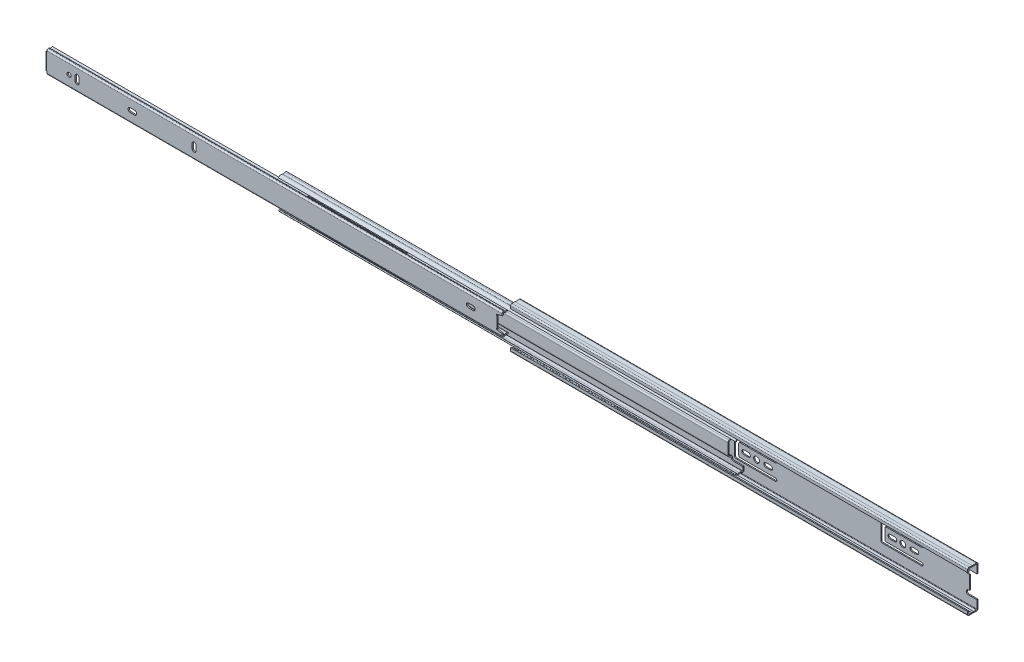
SolidWorks part; units mm, degrees
ref_plane "Front" through (0, 0, 0) normal (0, 0, 1) x (1, 0, 0)
ref_plane "Top" through (0, 0, 0) normal (0, 1, 0) x (1, 0, 0)
ref_plane "Right" through (0, 0, 0) normal (1, 0, 0) x (0, 0, -1)
sketch "Sketch1" plane through (0, 0, 0) normal (1, 0, 0) x (0, 0, -1)
  line L1 (5.6388, 0) -> (-5.6388, 0) construction
  line L4 (-4.1393, 22.8203) -> (-0.7433, 22.6989)
  line L5 (-1.1312, 21.5182) -> (-4.1819, 21.6273)
  line L6 (-4.445, 18.415) -> (-5.6388, 18.415)
  line L7 (-4.445, 21.3734) -> (-4.445, 18.415)
  line L8 (-5.6388, 18.415) -> (-5.6388, 21.3734)
  line L9 (3.9237, 21.6269) -> (0.7619, 21.5441)
  line L10 (5.6388, 0) -> (5.6388, 21.1191)
  line L11 (4.445, 21.1191) -> (4.445, 0)
  line L12 (5.6388, 0) -> (4.445, 0)
  line L13 (-0.7433, 22.6989) -> (3.8925, 22.8203)
  arc A0 (-4.445, 21.3734) -> (-4.1819, 21.6273) centre (-4.191, 21.3734) cw
  arc A1 (-5.6388, 21.3734) -> (-4.1393, 22.8203) centre (-4.191, 21.3734) cw
  arc A3 (3.9237, 21.6269) -> (4.445, 21.1191) centre (3.937, 21.1191) cw
  arc A4 (3.8925, 22.8203) -> (5.6388, 21.1191) centre (3.937, 21.1191) cw
  arc A5 (-1.1312, 21.5182) -> (0.7619, 21.5441) centre (-0.1524, 19.1744) cw
  dimension "D2" = 19.1744
  dimension "D7" = 0.254
  dimension "D8" = 0.508
  dimension "D6" = 2.54
  dimension "D9" = 1.1938
  dimension "D10" = 88.5
  dimension "D1" = 11.2776
  dimension "D3" = 5.7912
  dimension "D4" = 36.83
  dimension "D5" = 1.1938
  dimension "D11" = 87.953
  dimension "D12" = 45.6406
extrude "Extrude1" add sketch "Sketch1" along normal mid plane 500.126
ref_plane "Travel / 2" through (-504.063, 0, 0) normal (-1, 0, 0) x (0, 0, 1)
sketch "Sketch2" plane through (-504.063, 0, 0) normal (-1, 0, 0) x (0, 0, 1)
  line L0 (0.0254, 6.1159) -> (0.0254, 0)
  line L2 (-5.6388, 0) -> (5.6388, 0) construction
  line L3 (5.6388, 21.3734) -> (5.6388, 18.415) construction
  line L7 (-4.445, 21.1191) -> (-4.445, 0) construction
  line L8 (-5.6388, 0) -> (-5.6388, 21.1191) construction
  line L13 (-3.5306, 16.3766) -> (-3.5306, 9.5217)
  line L46 (-2.3867, 7.7262) -> (-0.4146, 6.8065)
  arc A0 (0.0254, 6.1159) -> (-0.4146, 6.8065) centre (-0.7366, 6.1159) ccw
  arc A1 (-1.5056, 17.2916) -> (1.2415, 16.9143) centre (0.1524, 19.1744) ccw
  arc A4 (1.1312, 21.5182) -> (-0.7619, 21.5441) centre (0.1524, 19.1744) ccw construction
  arc A19 (-3.5306, 9.5217) -> (-2.3867, 7.7262) centre (-1.5494, 9.5217) ccw
  arc A25 (-1.5056, 17.2916) -> (-3.5306, 16.3766) centre (-2.3114, 16.3766) ccw
  arc A51 (5.7404, 15.6277) -> (1.2415, 16.9143) centre (2.7686, 13.7451) ccw
  dimension "D2" = 8.4074
  dimension "D3" = 27.4903
  dimension "D6" = 1.9812
  dimension "D8" = 12.2319
  dimension "D10" = 2.5088
  dimension "D11" = 1.2192
  dimension "D4" = 0.762
  dimension "D5" = 4.4704
  dimension "D7" = 115
  dimension "D9" = 19.0435
  dimension "D13" = 11.3792
extrude "Middle Member" add sketch "Sketch2" against normal blind 500.126 separate body thin thin type one direction reverse wall 1.2192
ref_plane "Travel" through (-758.063, 0, 0) normal (-1, 0, 0) x (0, 0, 1)
sketch "Sketch3" plane through (-758.063, 0, 0) normal (-1, 0, 0) x (0, 0, 1)
  line L0 (1.2446, 0) -> (0.0254, 0) construction
  line L1 (-5.6388, 0) -> (-5.6388, 21.1191) construction
  line L56 (7.0612, 0) -> (7.0612, 10.6235)
  line L93 (5.5372, 12.1475) -> (5.1643, 12.1475)
  arc A0 (1.2082, 11.9072) -> (4.2365, 11.8325) centre (2.7686, 13.7451) ccw
  arc A29 (7.0612, 10.6235) -> (5.5372, 12.1475) centre (5.5372, 10.6235) ccw
  arc A53 (5.1643, 12.1475) -> (4.2365, 11.8325) centre (5.1643, 10.6235) ccw
  dimension "D1" = 1.524
  dimension "D4" = 1.524
  dimension "D5" = 2.411
  dimension "D2" = 12.7
  dimension "D3" = 12.1475
  dimension "D6" = 5.853
extrude "Drawer Member" add sketch "Sketch3" against normal blind 500.126 thin thin type one direction wall 1.397
sketch "Sketch6" plane through (0, 0, 7.0612) normal (0, 0, 1) x (1, 0, 0)
  line L1 (-758.063, 0) -> (-756.158, 0)
  line L2 (-758.063, 0) -> (-758.063, 12.1475)
  line L3 (-758.063, 12.1475) -> (-756.158, 12.1475)
  line L4 (-756.158, 0) -> (-756.158, 12.1475)
  line L5 (-257.937, 12.1475) -> (-758.063, 12.1475) construction
  line L7 (-758.063, 10.6235) -> (-758.063, 0) construction
  line L8 (-257.937, 0) -> (-758.063, 0) construction
  dimension "D1" = 1.905
extrude "Cut-Extrude1" cut sketch "Sketch6" against normal through all
sketch "Sketch7" plane through (0, 0, 0) normal (0, -1, 0) x (1, 0, 0)
  line L0 (-756.158, 7.0612) -> (-756.412, 7.0612)
  line L1 (-758.063, 5.4102) -> (-758.063, 0.3041)
  line L2 (-758.063, 0.3041) -> (-756.666, 0.3041)
  line L3 (-756.666, 0.3041) -> (-756.666, 5.4102)
  line L4 (-756.412, 5.6642) -> (-756.158, 5.6642)
  line L5 (-257.937, 5.6642) -> (-756.158, 5.6642) construction
  line L6 (-756.158, 7.0612) -> (-756.158, 5.6642)
  line L7 (-257.937, 0.3041) -> (-756.158, 0.3041) construction
  line L9 (-756.158, 5.087) -> (-756.158, 0.3041) construction
  arc A0 (-756.412, 5.6642) -> (-756.666, 5.4102) centre (-756.412, 5.4102) ccw
  arc A1 (-756.412, 7.0612) -> (-758.063, 5.4102) centre (-756.412, 5.4102) ccw
  dimension "D1" = 0.254
  dimension "D2" = 1.905
extrude "Extrude4" add sketch "Sketch7" against normal blind 8.89
sketch "Sketch8" plane through (0, 0, -4.445) normal (0, 0, 1) x (1, 0, 0)
  line L0 (240.4245, 7.6456) -> (241.8588, 7.493)
  line L1 (250.063, 12.2048) -> (240.6664, 12.2048)
  line L2 (241.8588, 7.493) -> (241.8588, 0)
  line L3 (250.063, 0) -> (-250.063, 0) construction
  line L4 (250.063, 21.1191) -> (250.063, 0) construction
  line L5 (250.063, 12.2048) -> (250.063, 0)
  line L6 (250.063, 0) -> (241.8588, 0)
  arc A0 (240.6664, 12.2048) -> (240.4245, 7.6456) centre (240.6664, 9.9188) ccw
  dimension "D3" = 9.9188
  dimension "D1" = 12.2048
  dimension "D2" = 8.2042
  dimension "D4" = 9.3966
  dimension "D5" = 7.493
extrude "Cut-Extrude2" cut sketch "Sketch8" against normal up to next (1.1938 mm away)
sketch "Sketch11" plane through (0, 0, 7.0612) normal (0, 0, 1) x (1, 0, 0)
  line L0 (-263.652, 5.9678) -> (-263.652, 0)
  line L8 (-257.937, 8.5893) -> (-263.7963, 7.2212)
  line L11 (-263.652, 0) -> (-257.937, 0)
  line L12 (-257.937, 0) -> (-257.937, 8.5893)
  arc A1 (-263.7963, 7.2212) -> (-263.652, 5.9678) centre (-263.6519, 6.6028) ccw
  dimension "D3" = 0.635
  dimension "D1" = 5.715
  dimension "D2" = 8.5893
  dimension "D4" = 5.9678
  dimension "D5" = 103.143
extrude "Cut-Extrude3" cut sketch "Sketch11" against normal up to next (1.397 mm away)
sketch "Sketch12" plane through (0, 0, 1.2446) normal (0, 0, 1) x (1, 0, 0)
  line L0 (-3.937, 12.065) -> (-14.097, 12.065)
  line L1 (-3.937, 16.3766) -> (-3.937, 9.5217) construction
  line L2 (-16.637, 9.525) -> (-16.637, 0)
  line L3 (-3.937, 0) -> (-504.063, 0) construction
  line L4 (-16.637, 0) -> (-3.937, 0)
  line L5 (-3.937, 0) -> (-3.937, 12.065)
  arc A0 (-14.097, 12.065) -> (-16.637, 9.525) centre (-14.097, 9.525) ccw
  point P11 (-16.637, 12.065)
  dimension "D3" = 2.54
  dimension "D1" = 12.7
  dimension "D2" = 12.065
extrude "Cut-Extrude4" cut sketch "Sketch12" against normal through all
sketch "Sketch13" plane through (0, 0, -4.445) normal (0, 0, 1) x (1, 0, 0)
  line L0 (-181.6747, 7.112) -> (-206.5032, 7.112)
  line L1 (241.8588, 0) -> (-250.063, 0) construction
  line L2 (-189.7646, 0) -> (-189.7646, 4.2392) construction
  line L3 (-232.6017, 10.287) -> (-181.6747, 10.287)
  line L4 (-250.063, 21.1191) -> (-250.063, 0) construction
  line L5 (-210.3132, 7.112) -> (-232.6017, 7.112)
  line L6 (-209.5512, 0) -> (-209.5512, 6.35)
  line L7 (-207.2652, 6.35) -> (-207.2652, 0)
  line L8 (-187.2881, 2.286) -> (-192.2411, 2.286)
  line L13 (-226.3406, 0) -> (-221.7686, 0)
  line L14 (-218.238, 0) -> (-211.888, 0)
  line L15 (-209.5512, 0) -> (-207.2652, 0)
  line L16 (-204.7506, 0) -> (-200.1786, 0)
  line L17 (-194.5271, 0) -> (-185.0021, 0)
  arc A1 (-232.6017, 10.287) -> (-232.6017, 7.112) centre (-232.6017, 8.6995) ccw
  arc A2 (-209.5512, 6.35) -> (-210.3132, 7.112) centre (-210.3132, 6.35) ccw
  arc A4 (-206.5032, 7.112) -> (-207.2652, 6.35) centre (-206.5032, 6.35) ccw
  arc A7 (-181.6747, 7.112) -> (-181.6747, 10.287) centre (-181.6747, 8.6995) ccw
  arc A8 (-211.888, 0) -> (-218.238, 0) centre (-215.063, 0) ccw
  arc A9 (-221.7686, 0) -> (-226.3406, 0) centre (-224.0546, 0) ccw
  arc A10 (-200.1786, 0) -> (-204.7506, 0) centre (-202.4646, 0) ccw
  arc A11 (-185.0021, 0) -> (-187.2881, 2.286) centre (-187.2881, 0) ccw
  arc A12 (-192.2411, 2.286) -> (-194.5271, 0) centre (-192.2411, 0) ccw
  dimension "D3" = 2.286
  dimension "D4" = 3.175
  dimension "D7" = 8.9916
  dimension "D8" = 21.59
  dimension "D9" = 34.29
  dimension "D10" = 0.762
  dimension "D11" = 17.5387
  dimension "D12" = 9.525
  dimension "D13" = 5.5118
  dimension "D14" = 35
  dimension "D1" = 3.175
  dimension "D2" = 50.927
  dimension "D5" = 2.286
  dimension "D6" = 10.287
extrude "Cut-Extrude5" cut sketch "Sketch13" against normal up to next (1.1938 mm away)
sketch "Sketch32" plane through (0, 0, -5.6388) normal (0, 0, -1) x (-1, 0, 0)
  line L0 (69.6005, 0) -> (79.1255, 0)
  line L1 (83.888, 0) -> (90.238, 0)
  line L2 (93.7305, 0) -> (103.2555, 0)
  line L3 (106.621, 0) -> (111.193, 0)
  line L4 (-241.8588, 0) -> (185.0021, 0) construction
  line L5 (232.6017, 10.287) -> (181.6747, 10.287) construction
  line L6 (181.6747, 7.112) -> (206.5032, 7.112) construction
  line L7 (98.493, 2.286) -> (98.493, -3.4269) construction
  line L8 (74.363, 2.286) -> (74.363, -3.4269) construction
  line L14 (66.4255, 10.287) -> (109.669, 10.287)
  line L15 (105.097, 7.112) -> (66.4255, 7.112)
  line L17 (111.193, 8.763) -> (111.193, 0)
  line L18 (106.621, 0) -> (106.621, 5.588)
  line L23 (71.8865, 2.286) -> (76.8395, 2.286)
  line L25 (96.0165, 2.286) -> (100.9695, 2.286)
  arc A0 (218.238, 0) -> (211.888, 0) centre (215.063, 0) ccw construction
  arc A13 (111.193, 8.763) -> (109.669, 10.287) centre (109.669, 8.763) ccw
  arc A14 (106.621, 5.588) -> (105.097, 7.112) centre (105.097, 5.588) ccw
  arc A17 (66.4255, 10.287) -> (66.4255, 7.112) centre (66.4255, 8.6995) ccw
  arc A20 (79.1255, 0) -> (76.8395, 2.286) centre (76.8395, 0) ccw
  arc A21 (71.8865, 2.286) -> (69.6005, 0) centre (71.8865, 0) ccw
  arc A22 (90.238, 0) -> (83.888, 0) centre (87.063, 0) ccw
  arc A24 (103.2555, 0) -> (100.9695, 2.286) centre (100.9695, 0) ccw
  arc A25 (96.0165, 2.286) -> (93.7305, 0) centre (96.0165, 0) ccw
  dimension "D2" = 1.524
  dimension "D3" = 3.175
  dimension "D4" = 9.525
  dimension "D5" = 2.286
  dimension "D6" = 11.43
  dimension "D7" = 12.7
  dimension "D8" = 24.13
  dimension "D9" = 20.6375
  dimension "D10" = 128
  dimension "D1" = 4.572
extrude "Cut-Extrude14" cut sketch "Sketch32" against normal up to next (1.1938 mm away)
sketch "Sketch33" plane through (83.6094, 0.8125, -5.6388) normal (0, 0, -1) x (-1, 0, 0)
  line L0 (57.2099, -0.8125) -> (66.7349, -0.8125)
  line L1 (71.4974, -0.8125) -> (77.8474, -0.8125)
  line L2 (81.3399, -0.8125) -> (90.8649, -0.8125)
  line L3 (94.2304, -0.8125) -> (98.8024, -0.8125)
  line L7 (86.1024, 1.4735) -> (86.1024, -4.2394) construction
  line L8 (61.9724, 1.4735) -> (61.9724, -3.4269) construction
  line L9 (-158.2494, -0.8125) -> (153.2099, -0.8125) construction
  line L10 (193.2784, 9.4745) -> (150.0349, 9.4745) construction
  line L11 (150.0349, 6.2995) -> (188.7064, 6.2995) construction
  line L14 (54.0349, 9.4745) -> (97.2784, 9.4745)
  line L15 (92.7064, 6.2995) -> (54.0349, 6.2995)
  line L17 (98.8024, 7.9505) -> (98.8024, -0.8125)
  line L18 (94.2304, -0.8125) -> (94.2304, 4.7755)
  line L23 (59.4959, 1.4735) -> (64.4489, 1.4735)
  line L25 (83.6259, 1.4735) -> (88.5789, 1.4735)
  arc A1 (301.8474, -0.8125) -> (295.4974, -0.8125) centre (298.6724, -0.8125) ccw construction
  arc A13 (98.8024, 7.9505) -> (97.2784, 9.4745) centre (97.2784, 7.9505) ccw
  arc A14 (94.2304, 4.7755) -> (92.7064, 6.2995) centre (92.7064, 4.7755) ccw
  arc A17 (54.0349, 9.4745) -> (54.0349, 6.2995) centre (54.0349, 7.887) ccw
  arc A20 (66.7349, -0.8125) -> (64.4489, 1.4735) centre (64.4489, -0.8125) ccw
  arc A21 (59.4959, 1.4735) -> (57.2099, -0.8125) centre (59.4959, -0.8125) ccw
  arc A22 (77.8474, -0.8125) -> (71.4974, -0.8125) centre (74.6724, -0.8125) ccw
  arc A24 (90.8649, -0.8125) -> (88.5789, 1.4735) centre (88.5789, -0.8125) ccw
  arc A25 (83.6259, 1.4735) -> (81.3399, -0.8125) centre (83.6259, -0.8125) ccw
  dimension "D2" = 1.524
  dimension "D3" = 3.175
  dimension "D4" = 9.525
  dimension "D5" = 2.286
  dimension "D6" = 11.43
  dimension "D7" = 12.7
  dimension "D8" = 24.13
  dimension "D9" = 20.6375
  dimension "D10" = 224
  dimension "D1" = 4.572
extrude "Cut-Extrude6" cut sketch "Sketch33" against normal up to next (1.1938 mm away)
sketch "Sketch34" plane through (169.8236, 1.4527, -5.6388) normal (0, 0, -1) x (-1, 0, 0)
  line L0 (-16.6239, -1.4527) -> (-7.0989, -1.4527)
  line L1 (-2.3364, -1.4527) -> (4.0136, -1.4527)
  line L2 (7.5061, -1.4527) -> (17.0311, -1.4527)
  line L3 (20.3966, -1.4527) -> (24.9686, -1.4527)
  line L4 (-72.0352, -1.4527) -> (143.4241, -1.4527) construction
  line L7 (12.2686, 0.8333) -> (12.2686, -4.8796) construction
  line L8 (-11.8614, 0.8333) -> (-11.8614, -4.0671) construction
  line L9 (279.4926, 8.8343) -> (236.2491, 8.8343) construction
  line L10 (236.2491, 5.6593) -> (274.9206, 5.6593) construction
  line L14 (-19.7989, 8.8343) -> (23.4446, 8.8343)
  line L15 (18.8726, 5.6593) -> (-19.7989, 5.6593)
  line L17 (24.9686, 7.3103) -> (24.9686, -1.4527)
  line L18 (20.3966, -1.4527) -> (20.3966, 4.1353)
  line L23 (-14.3379, 0.8333) -> (-9.3849, 0.8333)
  line L25 (9.7921, 0.8333) -> (14.7451, 0.8333)
  arc A0 (388.0616, -1.4527) -> (381.7116, -1.4527) centre (384.8866, -1.4527) ccw construction
  arc A13 (24.9686, 7.3103) -> (23.4446, 8.8343) centre (23.4446, 7.3103) ccw
  arc A14 (20.3966, 4.1353) -> (18.8726, 5.6593) centre (18.8726, 4.1353) ccw
  arc A17 (-19.7989, 8.8343) -> (-19.7989, 5.6593) centre (-19.7989, 7.2468) ccw
  arc A20 (-7.0989, -1.4527) -> (-9.3849, 0.8333) centre (-9.3849, -1.4527) ccw
  arc A21 (-14.3379, 0.8333) -> (-16.6239, -1.4527) centre (-14.3379, -1.4527) ccw
  arc A22 (4.0136, -1.4527) -> (-2.3364, -1.4527) centre (0.8386, -1.4527) ccw
  arc A24 (17.0311, -1.4527) -> (14.7451, 0.8333) centre (14.7451, -1.4527) ccw
  arc A25 (9.7921, 0.8333) -> (7.5061, -1.4527) centre (9.7921, -1.4527) ccw
  dimension "D2" = 1.524
  dimension "D3" = 3.175
  dimension "D4" = 9.525
  dimension "D5" = 2.286
  dimension "D6" = 11.43
  dimension "D7" = 12.7
  dimension "D8" = 24.13
  dimension "D9" = 20.6375
  dimension "D10" = 384.048
  dimension "D1" = 4.572
extrude "Cut E" cut sketch "Sketch34" against normal up to next (1.1938 mm away)
sketch "Sketch24" plane through (0, 0, 7.0612) normal (0, 0, 1) x (1, 0, 0)
  line L0 (-263.652, 0) -> (-756.412, 0) construction
  line L1 (-723.011, 4.826) -> (-723.011, 0) construction
  line L2 (-725.1954, 2.6416) -> (-725.1954, 0)
  line L3 (-725.1954, 0) -> (-720.8266, 0)
  line L4 (-720.8266, 0) -> (-720.8266, 2.6416)
  line L5 (-667.3215, 0) -> (-657.7965, 0)
  line L6 (-665.0355, 2.286) -> (-660.0825, 2.286)
  line L8 (-597.1954, 2.6416) -> (-597.1954, 0)
  line L9 (-597.1954, 0) -> (-592.8266, 0)
  line L10 (-592.8266, 0) -> (-592.8266, 2.6416)
  line L11 (-758.063, 8.89) -> (-758.063, 0) construction
  line L12 (-662.559, 2.286) -> (-662.559, 0) construction
  circle A0 centre (-731.901, 0) radius 2.1844
  arc A1 (-725.1954, 2.6416) -> (-720.8266, 2.6416) centre (-723.011, 2.6416) cw
  arc A2 (-667.3215, 0) -> (-665.0355, 2.286) centre (-665.0355, 0) cw
  arc A3 (-660.0825, 2.286) -> (-657.7965, 0) centre (-660.0825, 0) cw
  arc A4 (-597.1954, 2.6416) -> (-592.8266, 2.6416) centre (-595.011, 2.6416) cw
  dimension "D1" = 4.3688
  dimension "D4" = 8.89
  dimension "D5" = 2.286
  dimension "D7" = 60.452
  dimension "D8" = 128
  dimension "D2" = 35.052
  dimension "D3" = 4.826
  dimension "D6" = 9.525
extrude "Cut-Extrude13" cut sketch "Sketch24" against normal up to next (1.397 mm away)
sketch "Sketch25" plane through (0, 0, 7.0612) normal (0, 0, 1) x (1, 0, 0)
  line L1 (-263.652, 0) -> (-592.8266, 0) construction
  line L5 (-287.4645, 0) -> (-296.9895, 0)
  line L6 (-660.0825, 2.286) -> (-665.0355, 2.286) construction
  line L7 (-294.7035, 2.286) -> (-289.7505, 2.286)
  line L8 (-292.227, 0) -> (-292.227, 2.286) construction
  arc A1 (-720.8266, 2.6416) -> (-725.1954, 2.6416) centre (-723.011, 2.6416) ccw construction
  arc A3 (-294.7035, 2.286) -> (-296.9895, 0) centre (-294.7035, 0) ccw
  arc A4 (-289.7505, 2.286) -> (-287.4645, 0) centre (-289.7505, 0) cw
  arc A5 (-657.7965, 0) -> (-660.0825, 2.286) centre (-660.0825, 0) ccw construction
  dimension "D1" = 430.784
extrude "Cut D" cut sketch "Sketch25" against normal up to next (1.397 mm away)
sketch "Sketch36" plane through (0, 0, 7.0612) normal (0, 0, 1) x (1, 0, 0)
  line L0 (-309.1954, 0) -> (-304.8266, 0)
  line L1 (-304.8266, 0) -> (-304.8266, 2.6416)
  line L2 (-309.1954, 2.6416) -> (-309.1954, 0)
  line L4 (-296.9895, 0) -> (-592.8266, 0) construction
  line L5 (-720.8266, 0) -> (-720.8266, 2.6416) construction
  arc A0 (-304.8266, 2.6416) -> (-309.1954, 2.6416) centre (-307.011, 2.6416) ccw
  circle A1 centre (-319.711, 0) radius 2.1844
  arc A5 (-720.8266, 2.6416) -> (-725.1954, 2.6416) centre (-723.011, 2.6416) ccw construction
  dimension "D1" = 4.3688
  dimension "D2" = 416
  dimension "D3" = 12.7
extrude "Cut B" [suppressed] cut sketch "Sketch36" against normal up to next
sketch "Sketch38" plane through (0, 0, 7.0612) normal (0, 0, 1) x (1, 0, 0)
  line L0 (-501.1954, 0) -> (-501.1954, 2.6416)
  line L1 (-296.9895, 0) -> (-592.8266, 0) construction
  line L2 (-496.8266, 2.6416) -> (-496.8266, 0)
  line L3 (-496.8266, 0) -> (-501.1954, 0)
  line L4 (-720.8266, 0) -> (-720.8266, 2.6416) construction
  line L5 (-492.28, 0) -> (-484.406, 0)
  line L6 (-492.28, 0) -> (-492.28, 2.3749)
  line L7 (-492.28, 2.3749) -> (-484.406, 2.3749)
  line L8 (-484.406, 0) -> (-484.406, 2.3749)
  line L9 (-499.011, 7.182) -> (-499.011, -4.0911) construction
  line L10 (-505.742, 0) -> (-513.616, 0)
  line L11 (-505.742, 0) -> (-505.742, 2.3749)
  line L12 (-505.742, 2.3749) -> (-513.616, 2.3749)
  line L13 (-513.616, 0) -> (-513.616, 2.3749)
  line L14 (-488.343, 2.3749) -> (-488.343, -3.2385) construction
  arc A0 (-501.1954, 2.6416) -> (-496.8266, 2.6416) centre (-499.011, 2.6416) cw
  arc A1 (-720.8266, 2.6416) -> (-725.1954, 2.6416) centre (-723.011, 2.6416) ccw construction
  dimension "D4" = 224
  dimension "D1" = 7.874
  dimension "D2" = 2.3749
  dimension "D3" = 10.668
extrude "Cut A" [suppressed] cut sketch "Sketch38" against normal up to next
ref_plane "Plane3" through (-237.363, 0, 0) normal (-1, 0, 0) x (0, 0, 1)
sketch "Sketch27" plane through (-237.363, 0, 0) normal (-1, 0, 0) x (0, 0, 1)
  line L0 (0.1524, 21.6832) -> (0.1524, 16.6656)
  line L1 (0.1524, 23.635) -> (0.1524, 15.2838) construction
  arc A0 (0.1524, 16.6656) -> (0.1524, 21.6832) centre (0.1524, 19.1744) ccw
  arc A1 (-1.5056, 17.2916) -> (1.2415, 16.9143) centre (0.1524, 19.1744) ccw construction
revolve "Revolve1" add sketch "Sketch27" angle 360 about L1
pattern_linear "LPattern1" count 6 spacing 19.05 along (1, 0, 0) of bodies 128
sketch "Sketch28" plane through (-237.363, 0, 0) normal (-1, 0, 0) x (0, 0, 1)
  line L0 (2.6612, 19.1744) -> (-2.3564, 19.1744) construction
  line L1 (3.9624, 18.7934) -> (-3.6576, 18.7934)
  line L2 (3.9624, 18.7934) -> (3.9624, 19.5554)
  line L3 (3.9624, 19.5554) -> (-3.6576, 19.5554)
  line L4 (-3.6576, 18.7934) -> (-3.6576, 19.5554)
  line L5 (0.1524, 20.5465) -> (0.1524, 17.804) construction
  circle A1 centre (0.1524, 19.1744) radius 2.5088 construction
  point P8 (0.1524, 19.1744)
  dimension "D1" = 7.62
  dimension "D2" = 0.762
extrude "Extrude7" add sketch "Sketch28" along normal blind 6.35 and the other way blind 101.6
ref_plane "Plane4" through (-465.963, 0, 0) normal (-1, 0, 0) x (0, 0, 1)
sketch "Sketch29" plane through (-465.963, 0, 0) normal (-1, 0, 0) x (0, 0, 1)
  line L0 (2.7686, 16.0438) -> (2.7686, 11.4464)
  line L1 (2.7686, 16.6801) -> (2.7686, 10.2973) construction
  arc A0 (2.7686, 11.4464) -> (2.7686, 16.0438) centre (2.7686, 13.7451) ccw
  arc A1 (4.7105, 14.9753) -> (1.7707, 15.816) centre (2.7686, 13.7451) ccw construction
revolve "Revolve2" add sketch "Sketch29" angle 360 about L1
pattern_linear "LPattern2" count 6 spacing 19.05 along (1, 0, 0) of bodies 135
sketch "Sketch30" plane through (-465.963, 0, 0) normal (-1, 0, 0) x (0, 0, 1)
  line L0 (0.4699, 13.7451) -> (5.0673, 13.7451) construction
  line L1 (3.9624, 18.7934) -> (3.9624, 19.5554) construction
  line L2 (0.2286, 14.1261) -> (5.3086, 14.1261)
  line L3 (0.2286, 14.1261) -> (0.2286, 13.3641)
  line L4 (0.2286, 13.3641) -> (5.3086, 13.3641)
  line L5 (5.3086, 14.1261) -> (5.3086, 13.3641)
  line L7 (2.7686, 14.2437) -> (2.7686, 12.7853) construction
  circle A0 centre (2.7686, 13.7451) radius 2.2987 construction
  point P4 (2.7686, 13.7451)
  dimension "D1" = 5.08
extrude "Extrude8" add sketch "Sketch30" along normal blind 6.35 and the other way blind 101.6
mirror "Mirror3" about plane through (0, 0, 0) normal (0, 1, 0) of bodies 126 119 164 117 124 127 159
mirror "Mirror5" about plane through (0, 0, 0) normal (0, 1, 0) of bodies 141 134
